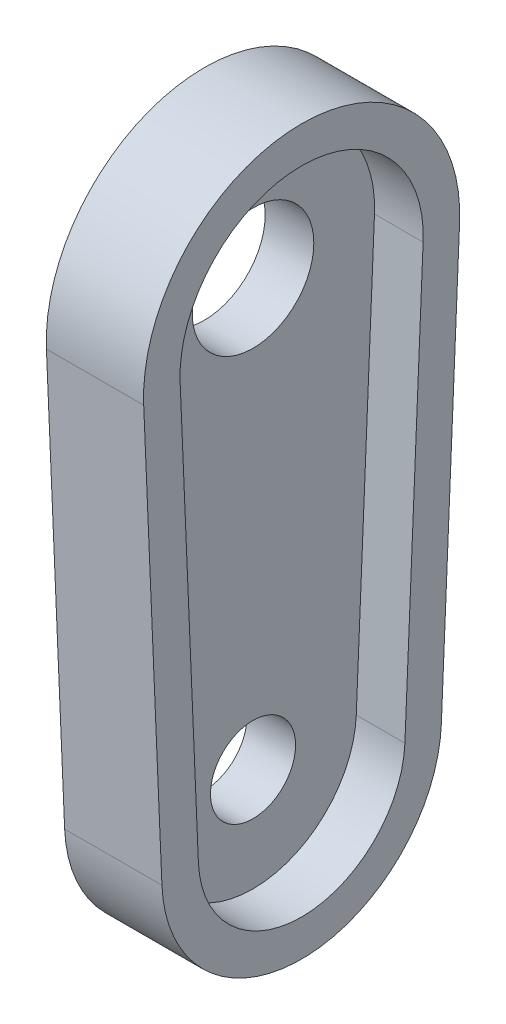
SolidWorks part; units mm, degrees
ref_plane "Спереди" through (0, 0, 0) normal (0, 0, 1) x (1, 0, 0)
ref_plane "Сверху" through (0, 0, 0) normal (0, 1, 0) x (1, 0, 0)
ref_plane "Справа" through (0, 0, 0) normal (1, 0, 0) x (0, 0, -1)
sketch "Эскиз1" plane through (0, 0, 0) normal (1, 0, 0) x (0, 0, -1)
  line L0 (0, 0) -> (0, -35) construction
  line L1 (-4.9954, -0.2143) -> (-3.4968, -35.15)
  line L2 (4.9954, -0.2143) -> (3.4968, -35.15)
  line L3 (-7.9926, -0.3429) -> (-6.494, -35.2786)
  line L4 (7.9926, -0.3429) -> (6.494, -35.2786)
  line L5 (-12.9881, -0.5571) -> (-11.4894, -35.4929)
  line L6 (12.9881, -0.5571) -> (11.4894, -35.4929)
  circle A0 centre (0, 0) radius 5
  circle A1 centre (0, -35) radius 3.5
  circle A2 centre (0, 0) radius 8
  circle A3 centre (0, -35) radius 6.5
  circle A4 centre (0, 0) radius 13
  circle A5 centre (0, -35) radius 11.5
  dimension "D1" = 10
  dimension "D2" = 7
  dimension "D3" = 35
  dimension "D4" = 3
  dimension "D5" = 3
  dimension "D6" = 5
  dimension "D7" = 5
extrude "Бобышка-Вытянуть1" add sketch "Эскиз1" along normal blind 4 contours A4 L3 A2 L4 | A2 L1 A0 L2 | L0 A0 L1 A2 | A0 L0 A2 L2 | A2 L0 A4 L2 | L2 A4 L4 A2 | L0 A2 L1 A4 | L3 A4 L1 A2 | A5 L1 A4 L3 | A5 L3 A4 L5 | L0 A4 L1 A5 | A4 L0 A5 L2 | A5 L4 A4 L2 | A5 L6 A4 L4 | L3 A5 L4 A3 | L1 A3 L2 A1 | L1 A5 L3 A3 | L0 A5 L1 A3 | A5 L0 A3 L2 | L0 A3 L1 A1 | A3 L0 A1 L2 | L4 A5 L2 A3 region at (0, -5.6092, -2.6103) region at (0, -5.6092, 2.6103) region at (0, -10.0891, -2.3462) region at (0, -10.0891, 2.3462) region at (0, -3.3432, 5.077) region at (0, -18.1332, -2.1616) region at (0, -18.1332, 2.1616) region at (0, -7.925, 6.279) region at (0, -7.925, -6.279) region at (0, -26.2897, -1.9604) region at (0, -26.2897, 1.9604) region at (0, -18.1969, 5.785) region at (0, -18.1969, -5.785) region at (0, -5.4767, 8.1238) region at (0, -30.6574, -1.9636) region at (0, -30.6574, 1.9636) region at (0, -28.2476, -5.401) region at (0, -28.2476, 5.401) region at (0, -18.1526, 10.0316) region at (0, -18.1526, -10.0316) region at (0, -32.0815, -5.6106) region at (0, -29.9958, -10.0093)
extrude "Бобышка-Вытянуть2" add sketch "Эскиз1<5>" along normal blind 8 contours A5 L3 A4 L5 | L3 A5 L4 A3 | A5 L6 A4 L4 | A4 L3 A2 L4 region at (0, -5.4767, 8.1238) region at (0, -18.1526, 10.0316) region at (0, -30.5528, 7.0065) region at (0, -18.1526, -10.0316)
sketch "Эскиз1<5>" plane through (0, 0, 0) normal (1, 0, 0) x (0, 0, -1) same geometry as "Эскиз1"
sketch "Эскиз2" plane through (8, 0, 0) normal (1, 0, 0) x (0, 0, -1)
  line L6 (-9.9908, -0.4286) -> (-8.4922, -35.3643)
  line L7 (8.4922, -35.3643) -> (9.9908, -0.4286)
  line L8 (-9.9908, -0.4286) -> (-8.4922, -35.3643)
  line L9 (8.4922, -35.3643) -> (9.9908, -0.4286)
  arc A8 (-8.4922, -35.3643) -> (8.4922, -35.3643) centre (0, -35) ccw
  arc A9 (9.9908, -0.4286) -> (-9.9908, -0.4286) centre (0, 0) ccw
  arc A10 (-8.4922, -35.3643) -> (8.4922, -35.3643) centre (0, -35) ccw
  arc A11 (9.9908, -0.4286) -> (-9.9908, -0.4286) centre (0, 0) ccw
  dimension "D1" = 2
extrude "Вырез-Вытянуть1" cut sketch "Эскиз2" against normal up to surface (4 mm away) up to face at (4, 0, -5)
